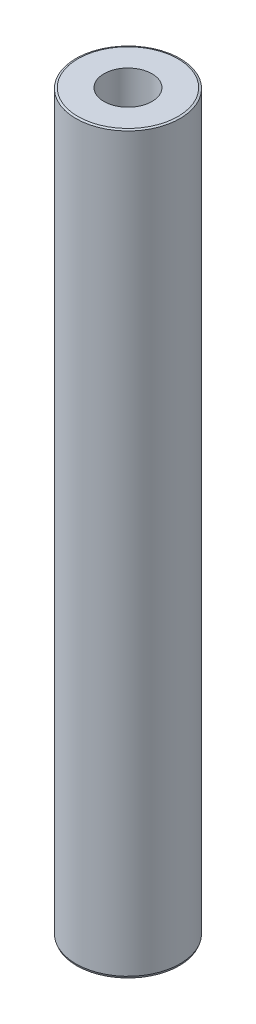
SolidWorks part; units mm, degrees
ref_plane "Front Plane" through (0, 0, 0) normal (0, 0, 1) x (1, 0, 0)
ref_plane "Top Plane" through (0, 0, 0) normal (0, 1, 0) x (1, 0, 0)
ref_plane "Right Plane" through (0, 0, 0) normal (1, 0, 0) x (0, 0, -1)
sketch "Sketch1" plane through (0, 0, 0) normal (0, 1, 0) x (1, 0, 0)
  circle A0 centre (0, 0) radius 42.5
  dimension "SHAFT_OD" = 85
extrude "Boss-Extrude1" add sketch "Sketch1" along normal blind 600
sketch "Sketch2" plane through (0, 0, 0) normal (0, 1, 0) x (1, 0, 0)
  circle A0 centre (0, 0) radius 19.6298
  dimension "BORE_D" = 39.2596
extrude "Cut-Extrude1" cut sketch "Sketch2" along normal through all
chamfer "Chamfer1" distance 0.6132 angle 69.624 2 edges at (0, 600, 42.5) (0, 0, 42.5) first distance on face at (0, 600, 42.5) first distance on face at (0, 0, 19.6298)
